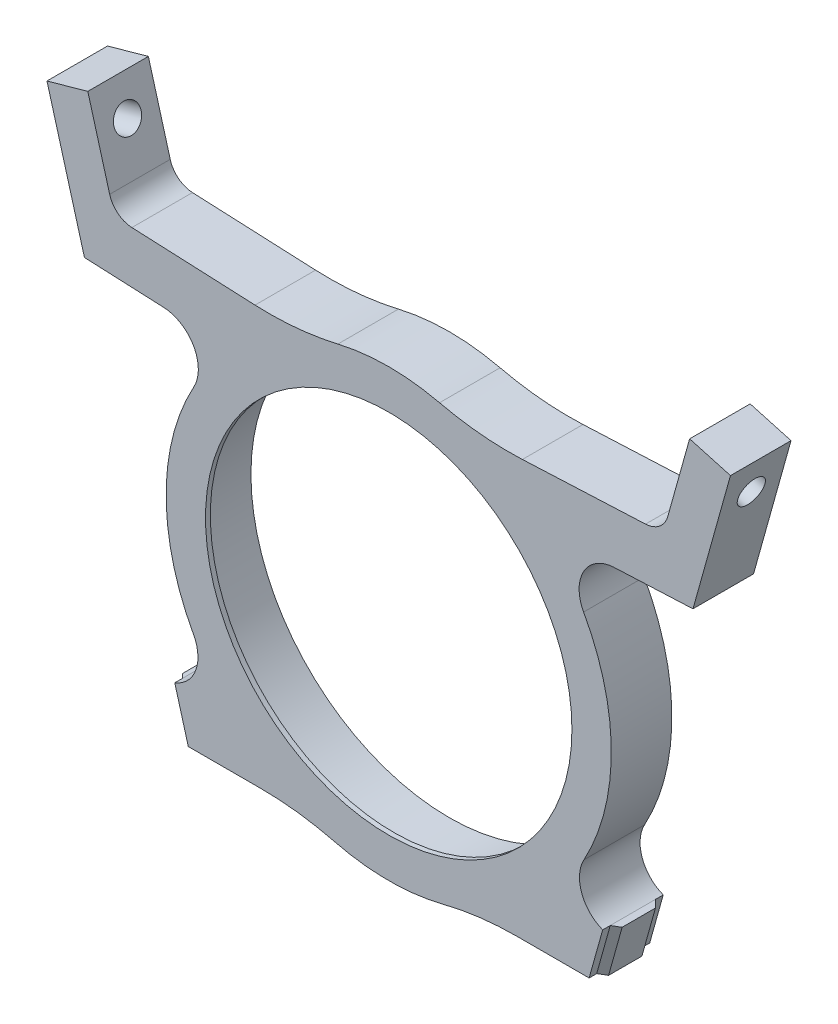
SolidWorks part; units mm, degrees
ref_plane "Ebene vorne" through (0, 0, 0) normal (0, 0, 1) x (1, 0, 0)
ref_plane "Ebene oben" through (0, 0, 0) normal (0, 1, 0) x (1, 0, 0)
ref_plane "Ebene rechts" through (0, 0, 0) normal (1, 0, 0) x (0, 0, -1)
sketch "Skizze1" plane through (0, 0, 0) normal (0, 0, 1) x (1, 0, 0)
  line L0 (-13.6359, -34.1266) -> (-33.0896, -34.1266)
  line L5 (-80.7379, 136.3891) -> (0, -152.5424) construction
  line L6 (-33.0896, -34.1266) -> (-35.3251, -26.1266)
  line L7 (-35.3251, -26.1266) -> (-25.845, -26.1266)
  line L8 (0, 0) -> (-26.219, 0) construction
  line L9 (0, 0) -> (0, -14.2745) construction
  line L10 (35.3251, -26.1266) -> (25.845, -26.1266)
  line L11 (33.0896, -34.1266) -> (35.3251, -26.1266)
  line L12 (13.6359, -34.1266) -> (33.0896, -34.1266)
  line L13 (-50.2356, 27.2324) -> (-25.845, 26.1266)
  line L14 (-13.6359, 34.1266) -> (-45.295, 35.562)
  line L15 (-50.2356, 27.2324) -> (-52.6564, 35.8957)
  line L16 (13.6359, 34.1266) -> (45.295, 35.562)
  line L17 (50.2356, 27.2324) -> (52.6564, 35.8957)
  line L18 (50.2356, 27.2324) -> (25.845, 26.1266)
  line L19 (80.7379, 136.3891) -> (0, -152.5424) construction
  line L20 (52.6564, 35.8957) -> (56.4242, 49.3792)
  line L21 (56.4242, 49.3792) -> (49.6825, 51.2631)
  line L22 (49.6825, 51.2631) -> (45.295, 35.562)
  line L23 (-52.6564, 35.8957) -> (-56.4242, 49.3792)
  line L24 (-56.4242, 49.3792) -> (-49.6825, 51.2631)
  line L25 (-49.6825, 51.2631) -> (-45.295, 35.562)
  circle A0 centre (0, 0) radius 32.75
  arc A1 (-13.6359, -34.1266) -> (13.6359, -34.1266) centre (0, 0) ccw
  arc A2 (-25.845, 26.1266) -> (-25.845, -26.1266) centre (0, 0) ccw
  arc A3 (25.845, -26.1266) -> (25.845, 26.1266) centre (0, 0) ccw
  arc A4 (13.6359, 34.1266) -> (-13.6359, 34.1266) centre (0, 0) ccw
  dimension "D1" = 65.5
  dimension "D2" = 4
  dimension "D3" = 8
  dimension "D4" = 14
  dimension "D5" = 7
extrude "Aufsatz-Linear austragen1" add sketch "Skizze1" along normal blind 10
sketch "Skizze2" plane through (0, 0, 10) normal (0, 0, 1) x (1, 0, 0)
  circle A0 centre (0, 0) radius 30.25
  circle A1 centre (0, 0) radius 32.75 construction
  circle A2 centre (0, 0) radius 32.75
  dimension "D1" = 2.5
extrude "Aufsatz-Linear austragen2" add sketch "Skizze2" against normal blind 0.8
sketch "Skizze5" plane through (32.7968, -9.1646, 0) normal (-0.9631, 0.2691, 0) x (0, 0, 1)
  line L0 (5, 62.7426) -> (5, 46.44) construction
  line L1 (10, 62.7426) -> (0, 62.7426) construction
  line L2 (10, 46.44) -> (0, 46.44) construction
  circle A0 centre (5, 56.9498) radius 2.25
  dimension "D1" = 4.5
extrude "Schnitt-Linear austragen1" cut sketch "Skizze5" against normal blind 10
mirror "Spiegeln1" about plane through (0, 0, 0) normal (1, 0, 0) of "Schnitt-Linear austragen1"
fillet "Verrundung1" radius 50 4 edges at (-13.6359, 34.1266, 5) (13.6359, 34.1266, 5) (-13.6359, -34.1266, 5) (13.6359, -34.1266, 5)
fillet "Verrundung2" radius 6 4 edges at (-25.845, -26.1266, 5) (25.845, -26.1266, 5) (25.845, 26.1266, 5) (-25.845, 26.1266, 5)
fillet "Verrundung3" radius 4 2 edges at (45.295, 35.562, 5) (-45.295, 35.562, 5)
ref_plane "Ebene1" through (6.4489, -23.0781, 0) normal (-0.2691, 0.9631, 0) x (0, 0, -1)
sketch "Skizze6" plane through (6.4489, -23.0781, 0) normal (-0.2691, 0.9631, 0) x (0, 0, -1)
  line L0 (-5, 41.0532) -> (-5, 46.0217) construction
  line L1 (-10, 41.0532) -> (0, 41.0532) construction
  line L2 (-8.75, 41.0532) -> (-7.75, 42.0532)
  line L3 (-7.75, 42.0532) -> (-2.25, 42.0532)
  line L4 (-1.25, 41.0532) -> (-2.25, 42.0532)
  line L5 (-1.25, 41.0532) -> (-8.75, 41.0532)
  point P9 (-5, 42.0532)
  dimension "D1" = 45
  dimension "D2" = 7.5
  dimension "D3" = 1
extrude "Aufsatz-Linear austragen3" add sketch "Skizze6" along normal up to vertex (8.3065 mm away) up to point (-35.3251, -26.1266, 10)
mirror "Spiegeln2" about plane through (0, 0, 0) normal (1, 0, 0) of "Aufsatz-Linear austragen3"
sketch "Skizze7" plane through (0, 0, 0) normal (0, 0, -1) x (-1, 0, 0)
  line L0 (-33.8757, -17.7881) -> (-22.0638, -36.7317)
  line L1 (-22.0638, -36.7317) -> (47.972, -39.4618)
  line L2 (47.972, -39.4618) -> (68.42, 54.1978)
  line L3 (68.42, 54.1978) -> (-64.4084, 52.8049)
  line L4 (-64.4084, 52.8049) -> (-52.1508, -13.7208)
  line L5 (-52.1508, -13.7208) -> (-33.8757, -17.7881)
extrude "Schnitt-Linear austragen2" [suppressed] cut sketch "Skizze7" against normal through all
